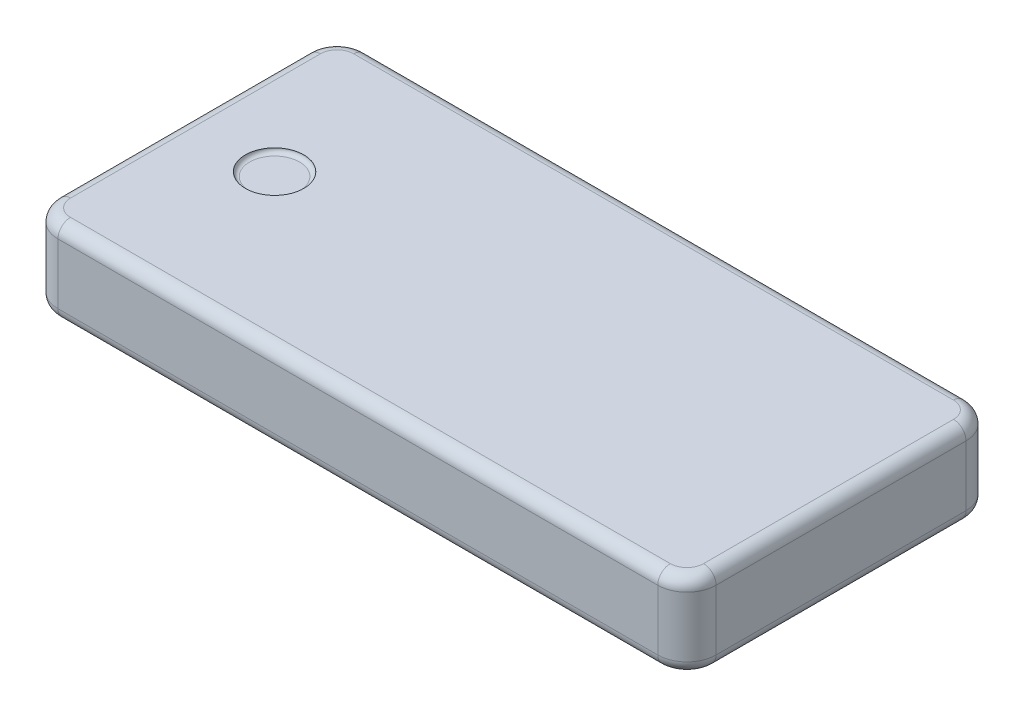
SolidWorks part; units mm, degrees
ref_plane "Front Plane" through (0, 0, 0) normal (0, 0, 1) x (1, 0, 0)
ref_plane "Top Plane" through (0, 0, 0) normal (0, 1, 0) x (1, 0, 0)
ref_plane "Right Plane" through (0, 0, 0) normal (1, 0, 0) x (0, 0, -1)
sketch "Sketch1" plane through (0, 0, 0) normal (0, 1, 0) x (1, 0, 0)
  line L1 (7, 0) -> (151, 0)
  line L2 (0, 7) -> (0, 67)
  line L3 (7, 74) -> (151, 74)
  line L4 (158, 7) -> (158, 67)
  arc A0 (151, 74) -> (158, 67) centre (151, 67) cw
  arc A1 (151, 0) -> (158, 7) centre (151, 7) ccw
  arc A2 (7, 0) -> (0, 7) centre (7, 7) cw
  arc A3 (0, 67) -> (7, 74) centre (7, 67) cw
  point P7 (158, 74)
  point P12 (0, 0)
  point P15 (0, 74)
  dimension "D3" = 7
  dimension "D1" = 74
  dimension "D2" = 158
extrude "Boss-Extrude1" add sketch "Sketch1" along normal blind 20.5
fillet "Fillet1" radius 3 16 edges at (2.0503, 0, -2.0503) (0, 0, -37) (2.0503, 0, -71.9497) (79, 0, -74) (155.9497, 0, -71.9497) (158, 0, -37) (155.9497, 0, -2.0503) (2.0503, 20.5, -2.0503) (0, 20.5, -37) (2.0503, 20.5, -71.9497) (79, 20.5, -74) (155.9497, 20.5, -71.9497) (158, 20.5, -37) (155.9497, 20.5, -2.0503) (79, 0, 0) (79, 20.5, 0)
sketch "Sketch2" plane through (0, 20.5, 0) normal (0, 1, 0) x (1, 0, 0)
  line L0 (3, 37) -> (22, 37) construction
  line L1 (3, 67) -> (3, 7) construction
  circle A0 centre (22, 37) radius 7
  point P6 (65.1505, 37)
  dimension "D2" = 14
  dimension "D1" = 19
extrude "Cut-Extrude1" cut sketch "Sketch2" against normal blind 1
fillet "Fillet2" radius 1 1 edges at (22, 19.5, -30)
